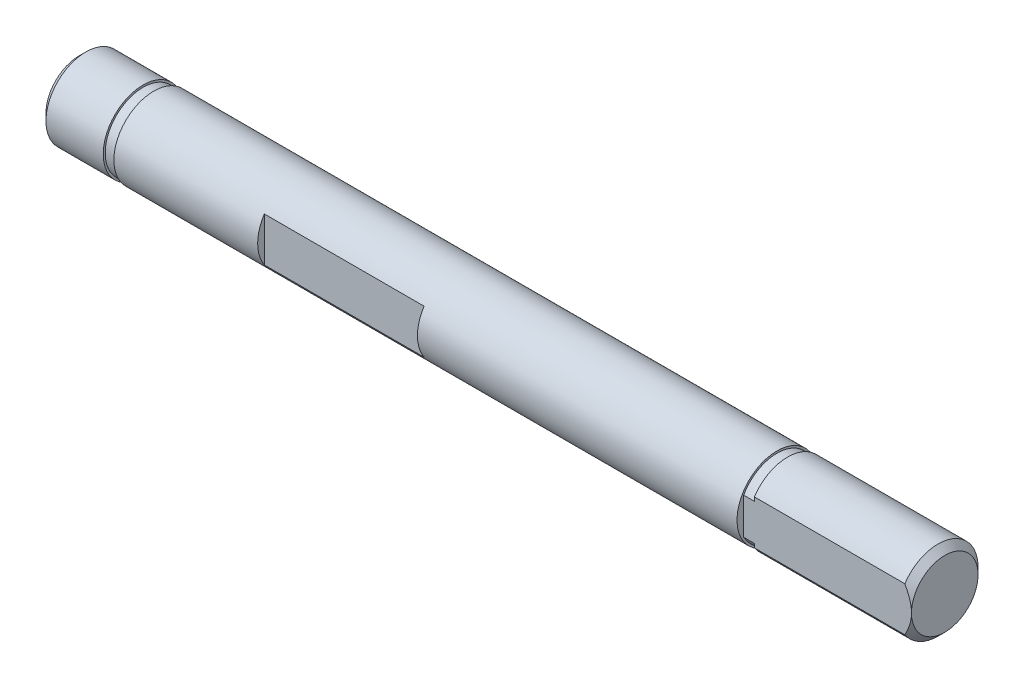
SolidWorks part; units mm, degrees
ref_plane "Alzado" through (0, 0, 0) normal (1, 0, 0) x (0, 1, 0)
ref_plane "Planta" through (0, 0, 0) normal (0, 0, 1) x (0, 1, 0)
ref_plane "Vista lateral" through (0, 0, 0) normal (0, 1, 0) x (-1, 0, 0)
sketch "Croquis1" plane through (0, 0, 0) normal (0, 1, 0) x (-1, 0, 0)
  line L0 (-32.5, 0) -> (-32.5, 3)
  line L1 (-32.5, 3) -> (-20.7, 3)
  line L2 (-20.7, 3) -> (-20.7, 2.85)
  line L3 (-20.7, 2.85) -> (-19.9, 2.85)
  line L4 (-19.9, 2.85) -> (-19.9, 3)
  line L5 (-19.9, 3) -> (26.9, 3)
  line L6 (32.5, 3) -> (32.5, 0)
  line L7 (-32.5, 0) -> (32.5, 0) construction
  line L9 (26.9, 3) -> (26.9, 2.85)
  line L10 (26.9, 2.85) -> (27.7, 2.85)
  line L11 (27.7, 2.85) -> (27.7, 3)
  line L12 (27.7, 3) -> (32.5, 3)
  line L13 (-32.5, 0) -> (32.5, 0)
  dimension "D2" = 6
  dimension "D8" = 0.8
  dimension "D1" = 4.8
  dimension "D7" = 65
  dimension "D3" = 48.4
  dimension "D4" = 5.7
revolve "Revolución1" add sketch "Croquis1" angle 360 about L7
chamfer "Chaflán1" distance 0.5 angle 45 2 edges at (-32.5, 0, -3) (32.5, 0, -3)
ref_plane "Plano1" through (-4.1, 0, 0) normal (1, 0, 0) x (0, 0, -1)
sketch "Croquis2" plane through (32.5, 0, 0) normal (1, 0, 0) x (0, 1, 0)
  line L3 (1.6583, 2.5) -> (-1.6583, 2.5)
  circle A1 centre (0, 0) radius 3 construction
  arc A4 (1.6583, 2.5) -> (-1.6583, 2.5) centre (0, 0) ccw
  point P4 (0, 3)
  dimension "D1" = 0.5
extrude "Cortar-Extruir1" cut sketch "Croquis2" against normal up to surface (12.6 mm away) up to face at (19.9, 0, -2.85)
extrude "Cortar-Extruir2" cut sketch "Croquis2<2>" against normal blind 12 from surface starting at plane "Plano1"
sketch "Croquis2<2>" plane through (32.5, 0, 0) normal (1, 0, 0) x (0, 1, 0) same geometry as "Croquis2"
chamfer "Chaflán2" [suppressed] distance 0.5 angle 45
equation "\"ancho_circlip\"=0.8"
equation "\"D8@Croquis1\"=\"ancho_circlip\""
equation "\"ranura_circlip\"=0.45"
equation "\"d_ranura\"=5.7"
equation "\"D4@Croquis1\"=\"d_ranura\""
